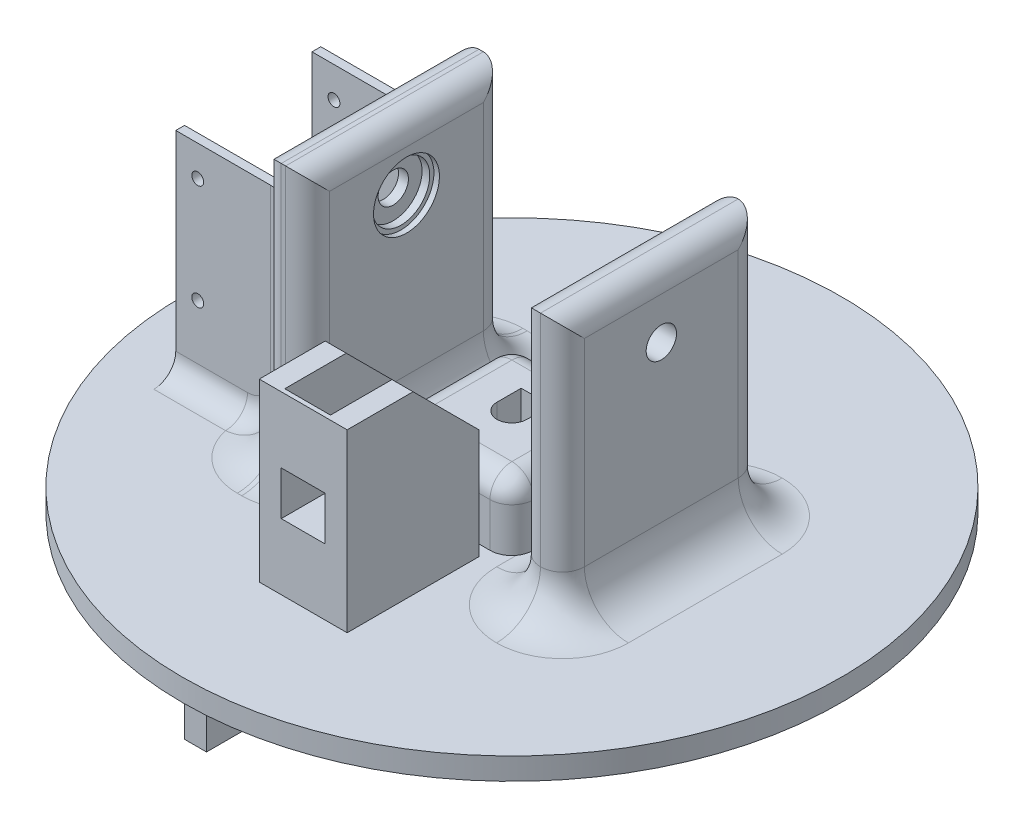
SolidWorks part; units mm, degrees
ref_plane "Plan de face" through (0, 0, 0) normal (0, 0, 1) x (1, 0, 0)
ref_plane "Plan de dessus" through (0, 0, 0) normal (0, 1, 0) x (1, 0, 0)
ref_plane "Plan de droite" through (0, 0, 0) normal (1, 0, 0) x (0, 0, -1)
sketch "Esquisse1" plane through (0, 0, 0) normal (0, 1, 0) x (1, 0, 0)
  circle A0 centre (0, 0) radius 46
  dimension "D1" = 92
extrude "Boss.-Extru.1" add sketch "Esquisse1" along normal blind 5
sketch "Esquisse4" plane through (0, 5, 0) normal (0, 1, 0) x (1, 0, 0)
  circle A0 centre (0, 0) radius 75
  dimension "D1" = 150
extrude "Boss.-Extru.2" add sketch "Esquisse4" along normal blind 5
sketch "Esquisse5" plane through (0, 10, 0) normal (0, 1, 0) x (1, 0, 0)
  line L1 (-34, -22.5) -> (34, -22.5)
  line L2 (-34, -22.5) -> (-34, 22.5)
  line L3 (-34, 22.5) -> (34, 22.5)
  line L4 (34, -22.5) -> (34, 22.5)
  line L5 (-34, -22.5) -> (34, 22.5) construction
  line L6 (-34, 22.5) -> (34, -22.5) construction
  point P0 (0, 0)
  dimension "D1" = 68
  dimension "D2" = 45
extrude "Boss.-Extru.3" add sketch "Esquisse5" along normal blind 60
sketch "Esquisse6" plane through (0, 0, 22.5) normal (0, 0, 1) x (1, 0, 0)
  line L0 (-34, 70) -> (34, 70) construction
  line L1 (-24, 70) -> (24, 70)
  line L2 (-24, 70) -> (-24, 10)
  line L3 (-24, 10) -> (24, 10)
  line L4 (24, 70) -> (24, 10)
  line L5 (-34, 10) -> (34, 10) construction
  line L6 (-34, 70) -> (-34, 10) construction
  dimension "D1" = 48
  dimension "D2" = 10
extrude "Enlèv. mat.-Extru.1" cut sketch "Esquisse6" against normal through all
sketch "Esquisse7" plane through (-34, 0, 0) normal (-1, 0, 0) x (0, 0, 1)
  line L0 (-22.5, 70) -> (22.5, 70) construction
  line L1 (-14.5, 68) -> (14.5, 68)
  line L2 (-14.5, 68) -> (-14.5, 20.5)
  line L3 (-14.5, 20.5) -> (14.5, 20.5)
  line L4 (14.5, 68) -> (14.5, 20.5)
  line L5 (-22.5, 70) -> (-22.5, 10) construction
  dimension "D1" = 29
  dimension "D2" = 47.5
  dimension "D3" = 2
  dimension "D4" = 8
extrude "Enlèv. mat.-Extru.2" cut sketch "Esquisse7" against normal blind 4.75
sketch "Esquisse8" plane through (-34, 0, 0) normal (-1, 0, 0) x (0, 0, 1)
  line L0 (-22.5, 10) -> (22.5, 10) construction
  line L1 (-16.5, 10) -> (-14.5, 10)
  line L2 (-16.5, 10) -> (-16.5, 58.5)
  line L3 (-16.5, 58.5) -> (-14.5, 58.5)
  line L4 (-14.5, 10) -> (-14.5, 58.5)
  line L5 (-14.5, 68) -> (-14.5, 20.5) construction
  line L6 (14.5, 20.5) -> (14.5, 68) construction
  line L7 (16.5, 10) -> (14.5, 10)
  line L8 (16.5, 10) -> (16.5, 58.5)
  line L9 (16.5, 58.5) -> (14.5, 58.5)
  line L10 (14.5, 10) -> (14.5, 58.5)
  line L11 (14.5, 68) -> (-14.5, 68) construction
  dimension "D1" = 2
  dimension "D2" = 2
  dimension "D3" = 9.5
  dimension "D4" = 9.5
extrude "Boss.-Extru.4" add sketch "Esquisse8" along normal blind 26
sketch "Esquisse9" plane through (-29.25, 0, 0) normal (-1, 0, 0) x (0, 0, 1)
  line L0 (14.5, 20.5) -> (14.5, 68) construction
  line L2 (-14.5, 20.5) -> (14.5, 20.5) construction
  circle A0 centre (0, 55.5) radius 3.45
  dimension "D1" = 6.9
  dimension "D2" = 14.5
  dimension "D3" = 35
extrude "Enlèv. mat.-Extru.3" cut sketch "Esquisse9" against normal through all
sketch "Esquisse11" plane through (-24, 0, 0) normal (1, 0, 0) x (0, 0, -1)
  circle A0 centre (0, 55.5) radius 6.55
  dimension "D1" = 13.1
extrude "Enlèv. mat.-Extru.5" cut sketch "Esquisse11" against normal blind 3
sketch "Esquisse12" plane through (-24, 0, 0) normal (1, 0, 0) x (0, 0, -1)
  circle A0 centre (0, 55.5) radius 7.5
  dimension "D1" = 15
extrude "Enlèv. mat.-Extru.6" cut sketch "Esquisse12" against normal blind 1.25
sketch "Esquisse13" plane through (24, 0, 0) normal (-1, 0, 0) x (0, 0, 1)
  circle A0 centre (0, 55.5) radius 6.55
  dimension "D1" = 13.1
extrude "Enlèv. mat.-Extru.7" cut sketch "Esquisse13" against normal blind 4
sketch "Esquisse14" plane through (24, 0, 0) normal (-1, 0, 0) x (0, 0, 1)
  circle A0 centre (0, 55.5) radius 7.5
  dimension "D1" = 15
extrude "Enlèv. mat.-Extru.8" cut sketch "Esquisse14" against normal blind 1.25
fillet "Congé1" radius 5 6 edges at (24, 40, 22.5) (24, 70, 0) (24, 40, -22.5) (-24, 40, -22.5) (-24, 70, 0) (-24, 40, 22.5)
fillet "Congé2" radius 5 3 edges at (34, 40, -22.5) (34, 70, 0) (34, 40, 22.5)
fillet "Congé3" radius 4 3 edges at (-34, 40, -22.5) (-34, 70, 0) (-34, 40, 22.5)
fillet "Congé5" radius 10 15 edges at (-32.8284, 10, -21.3284) (-29.5, 10, -22.5) (-25.4645, 10, -21.0355) (-32.8284, 10, 21.3284) (-29.5, 10, 22.5) (-25.4645, 10, 21.0355) (32.5355, 10, 21.0355) (25.4645, 10, 21.0355) (25.4645, 10, -21.0355) (32.5355, 10, -21.0355) (-24, 10, 0) (24, 10, 0) (34, 10, 0) (-34, 10, -17.5) (-34, 10, 17.5)
sketch "Esquisse15" plane through (0, 0, 0) normal (0, -1, 0) x (1, 0, 0)
  line L0 (-3.4, 0) -> (-3.4, -3.1)
  line L1 (-3.4, -3.1) -> (3.4, -3.1)
  line L2 (3.4, -3.1) -> (3.4, 0)
  arc A0 (3.4, 0) -> (-3.4, 0) centre (0, 0) ccw
  dimension "D1" = 3.4
  dimension "D2" = 3.1
extrude "Enlèv. mat.-Extru.9" cut sketch "Esquisse15" against normal through all both and the other way through all
sketch "Esquisse17" plane through (0, 10, 0) normal (0, 1, 0) x (1, 0, 0)
  line L1 (-15, -15) -> (15, -15)
  line L2 (-15, -15) -> (-15, 15)
  line L3 (-15, 15) -> (15, 15)
  line L4 (15, -15) -> (15, 15)
  line L5 (-15, -15) -> (15, 15) construction
  line L6 (-15, 15) -> (15, -15) construction
  point P0 (0, 0)
  dimension "D1" = 30
  dimension "D2" = 30
extrude "Boss.-Extru.5" add sketch "Esquisse17" along normal blind 15
sketch "Esquisse19" plane through (0, 10, 0) normal (0, -1, 0) x (1, 0, 0)
  line L0 (3.4, 0) -> (3.4, -3.1)
  line L1 (3.4, -3.1) -> (-3.4, -3.1) construction
  line L2 (3.4, -3.1) -> (-3.4, -3.1) construction
  line L3 (3.4, -3.1) -> (-3.4, -3.1)
  line L4 (-3.4, -3.1) -> (-3.4, 0)
  arc A0 (-3.4, 0) -> (3.4, 0) centre (0, 0) cw
extrude "Enlèv. mat.-Extru.11" cut sketch "Esquisse19" against normal through all
sketch "Esquisse20" plane through (0, 0, -15) normal (0, 0, -1) x (-1, 0, 0)
  line L0 (-15, 25) -> (15, 25) construction
  line L1 (15, 25) -> (15, 10.0501) construction
  circle A0 centre (0, 18) radius 1.4
  dimension "D1" = 2.8
  dimension "D2" = 7
  dimension "D3" = 15
extrude "Enlèv. mat.-Extru.12" cut sketch "Esquisse20" against normal blind 10
sketch "Esquisse21" plane through (0, 25, 0) normal (0, 1, 0) x (1, 0, 0)
  line L0 (-3.4, 0) -> (-3.4, 3.1) construction
  line L1 (3.4, 3.1) -> (-3.4, 3.1)
  line L2 (3.4, 3.1) -> (3.4, 5.5)
  line L3 (3.4, 5.5) -> (-3.4, 5.5)
  line L4 (-3.4, 3.1) -> (-3.4, 5.5)
  dimension "D1" = 2.4
extrude "Enlèv. mat.-Extru.13" cut sketch "Esquisse21" against normal blind 11
sketch "Esquisse23" plane through (0, 10, 0) normal (0, 1, 0) x (1, 0, 0)
  line L1 (-10, -17.5) -> (10, -17.5)
  line L2 (-10, -17.5) -> (-10, -47.5)
  line L3 (-10, -47.5) -> (10, -47.5)
  line L4 (10, -17.5) -> (10, -47.5)
  point P5 (0, -17.5)
  dimension "D1" = 30
  dimension "D2" = 20
  dimension "D3" = 17.5
extrude "Boss.-Extru.11" add sketch "Esquisse23" along normal blind 40 separate body
sketch "Esquisse24" plane through (0, 0, 0) normal (1, 0, 0) x (0, 0, -1)
  line L0 (-46.5, 40) -> (-24.1084, 18.6417)
  line L2 (-24.1084, 18.6417) -> (3.4924, 47.5778)
  line L3 (3.4924, 47.5778) -> (-18.2157, 68.2843)
  line L6 (-47.5, 50) -> (-17.5, 50) construction
  line L7 (-47.5, 50) -> (-47.5, 10) construction
  line L8 (-46.5, 40) -> (-46.5, 68.2843)
  line L9 (-46.5, 68.2843) -> (-18.2157, 68.2843)
  dimension "D1" = 40
  dimension "D2" = 30
  dimension "D3" = 10
  dimension "D4" = 1
  dimension "D5" = 28.2843
  dimension "D6" = 133.647
extrude "Enlèv. mat.-Extru.21" cut sketch "Esquisse24" against normal blind 5.2 and the other way blind 5.2
sketch "Esquisse25" plane through (0, 0, 0) normal (1, 0, 0) x (0, 0, -1)
  line L0 (-32.5, 50) -> (-17.5, 35)
  line L1 (-47.5, 50) -> (-17.5, 50) construction
  line L2 (-17.5, 65) -> (-17.5, 20) construction
  line L3 (-17.5, 35) -> (-17.5, 50)
  line L4 (-17.5, 50) -> (-32.5, 50)
  dimension "D1" = 45
extrude "Enlèv. mat.-Extru.22" cut sketch "Esquisse25" against normal blind 22.5 and the other way blind 22.5
sketch "Esquisse26" plane through (0, 0, 47.5) normal (0, 0, 1) x (1, 0, 0)
  line L0 (-10, 10) -> (10, 10) construction
  line L1 (-5, 35) -> (5, 35)
  line L2 (-5, 35) -> (-5, 25)
  line L3 (-5, 25) -> (5, 25)
  line L4 (5, 35) -> (5, 25)
  line L5 (-10, 50) -> (-10, 10) construction
  dimension "D1" = 15
  dimension "D2" = 10
  dimension "D3" = 5
  dimension "D4" = 10
extrude "Enlèv. mat.-Extru.23" cut sketch "Esquisse26" against normal blind 22.5
sketch "Esquisse27" plane through (0, 5, 0) normal (0, -1, 0) x (1, 0, 0)
  circle A1 centre (0, 0) radius 53
  circle A3 centre (0, 0) radius 50.55
  dimension "D1" = 101.1
  dimension "D2" = 106
extrude "Boss.-Extru.12" add sketch "Esquisse27" along normal blind 10
sketch "Esquisse28" plane through (0, 5, 0) normal (0, -1, 0) x (1, 0, 0)
  line L1 (-2.5, 72) -> (2.5, 72)
  line L2 (-2.5, 72) -> (-2.5, 52)
  line L3 (-2.5, 52) -> (2.5, 52)
  line L4 (2.5, 72) -> (2.5, 52)
  point P4 (0, 52)
  dimension "D1" = 20
  dimension "D2" = 5
  dimension "D3" = 52
extrude "Boss.-Extru.13" add sketch "Esquisse28" along normal blind 10
fillet "Congé7" radius 5 6 edges at (-34, 39.25, 16.5) (-36.9289, 12.9289, 16.5) (-34, 39.25, -16.5) (-36.9289, 12.9289, -16.5) (-52, 10, 16.5) (-52, 10, -16.5)
sketch "Esquisse31" plane through (0, 0, -16.5) normal (0, 0, -1) x (-1, 0, 0)
  line L0 (60, 58.5) -> (38.4853, 58.5) construction
  line L1 (60, 58.5) -> (60, 15) construction
  circle A0 centre (55, 51.5) radius 1.35
  circle A1 centre (55, 27.5) radius 1.35
  dimension "D1" = 2.7
  dimension "D2" = 7
  dimension "D3" = 5
  dimension "D4" = 24
extrude "Enlèv. mat.-Extru.24" cut sketch "Esquisse31" against normal through all
fillet "Congé11" radius 5 2 edges at (-15, 25, 0) (15, 25, 0)
fillet "Congé12" radius 5 5 edges at (15, 15.0251, -15) (13.5355, 23.5355, -15) (-15, 15.0251, -15) (-13.5355, 23.5355, -15) (0, 25, -15)
fillet "Congé13" radius 5 5 edges at (-15, 15.0251, 15) (-13.5355, 23.5355, 15) (15, 15.0251, 15) (13.5355, 23.5355, 15) (0, 25, 15)
